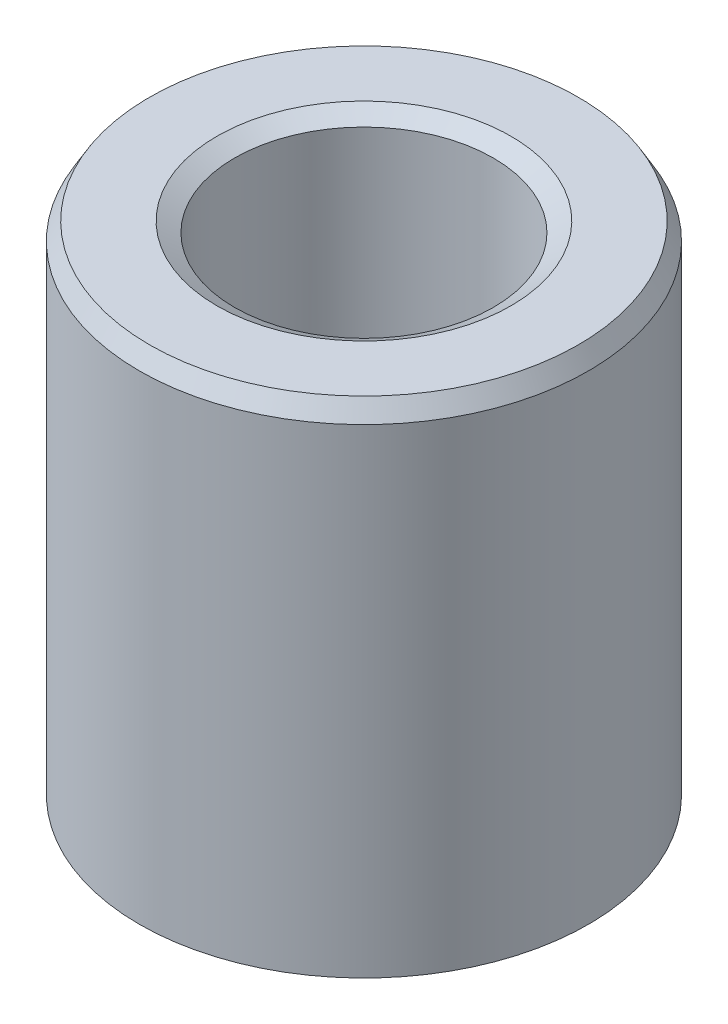
SolidWorks part; units mm, degrees
ref_plane "Front Plane" through (0, 0, 0) normal (0, 0, 1) x (1, 0, 0)
ref_plane "Top Plane" through (0, 0, 0) normal (0, 1, 0) x (1, 0, 0)
ref_plane "Right Plane" through (0, 0, 0) normal (1, 0, 0) x (0, 0, -1)
sketch "Sketch1" plane through (0, 0, 0) normal (0, 1, 0) x (1, 0, 0)
  circle A0 centre (0, 0) radius 47.5
  dimension "SLEEVE_OD" = 95
extrude "Boss-Extrude1" add sketch "Sketch1" along normal blind 107.2314
sketch "Sketch2" plane through (0, 0, 0) normal (0, 1, 0) x (1, 0, 0)
  circle A0 centre (0, 0) radius 27.3764
  dimension "BORE_D" = 54.7529
extrude "Cut-Extrude1" cut sketch "Sketch2" along normal through all
chamfer "Chamfer1" distance 3.7113 angle 30 4 edges at (0, 107.2314, 27.3764) (0, 0, 27.3764) (0, 0, 47.5) (0, 107.2314, 47.5) first distance on face at (0, 107.2314, 27.3764) first distance on face at (0, 0, 27.3764) first distance on face at (0, 107.2314, 47.5)
